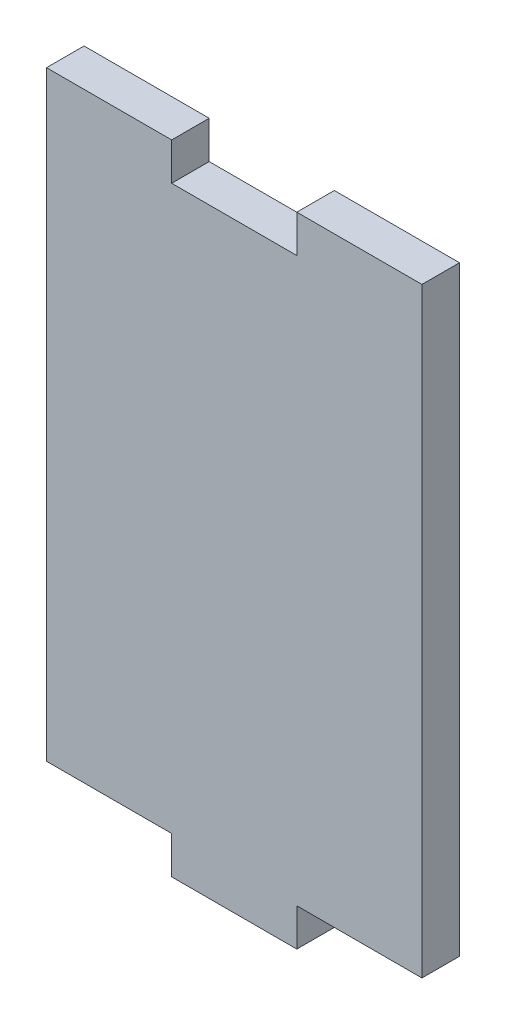
SolidWorks part; units mm, degrees
ref_plane "Front Plane" through (0, 0, 0) normal (0, 0, 1) x (1, 0, 0)
ref_plane "Top Plane" through (0, 0, 0) normal (0, 1, 0) x (1, 0, 0)
ref_plane "Right Plane" through (0, 0, 0) normal (1, 0, 0) x (0, 0, -1)
sketch "Sketch1" plane through (0, 0, 0) normal (0, 0, 1) x (1, 0, 0)
  line L0 (0, 0) -> (-10, 0)
  line L1 (-10, 0) -> (-10, -3)
  line L2 (-10, -3) -> (-20, -3)
  line L3 (-20, -3) -> (-20, 0)
  line L4 (-20, 0) -> (-30, 0)
  line L5 (-30, 0) -> (-30, 48)
  line L6 (-30, 48) -> (-20, 48)
  line L7 (-20, 48) -> (-20, 45)
  line L8 (-20, 45) -> (-10, 45)
  line L9 (-10, 45) -> (-10, 48)
  line L10 (-10, 48) -> (0, 48)
  line L11 (0, 48) -> (0, 0)
  dimension "D1" = 10
  dimension "D2" = 10
  dimension "D3" = 10
  dimension "D4" = 48
  dimension "D5" = 10
  dimension "D6" = 10
  dimension "D7" = 3
  dimension "D8" = 3
  dimension "D9" = 3
extrude "Boss-Extrude1" add sketch "Sketch1" along normal blind 3
